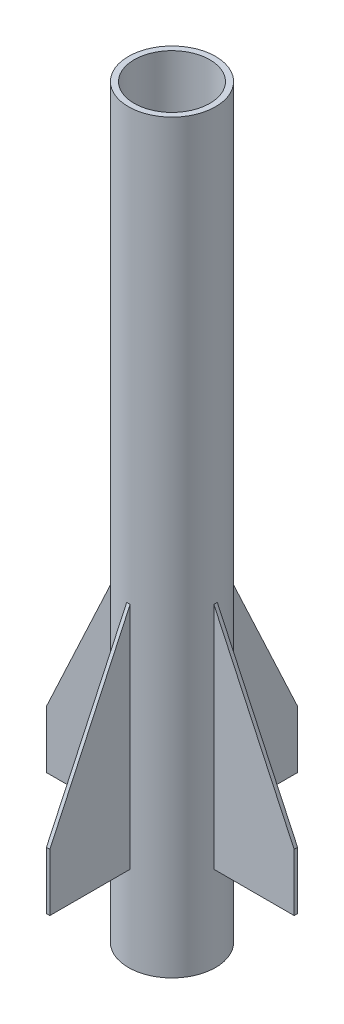
SolidWorks part; units mm, degrees
ref_plane "Front Plane" through (0, 0, 0) normal (0, 0, 1) x (1, 0, 0)
ref_plane "Top Plane" through (0, 0, 0) normal (0, 1, 0) x (1, 0, 0)
ref_plane "Right Plane" through (0, 0, 0) normal (1, 0, 0) x (0, 0, -1)
sketch "Sketch1" plane through (0, 0, 0) normal (0, 0, 1) x (1, 0, 0)
  line L0 (76, 0) -> (76, 1300)
  line L1 (0, 0) -> (0, 2000) construction
  line L9 (66, 0) -> (66, 1300)
  line L10 (76, 0) -> (66, 0)
  line L11 (76, 1300) -> (66, 1300)
  point P7 (65, 1600)
  point P8 (-1029.1667, 1600)
  point P9 (-9.3208, 1996.3774)
  dimension "D1" = 1300
  dimension "D2" = 76
  dimension "D3" = 2000
  dimension "D4" = 10
revolve "Revolve1" add sketch "Sketch1" angle 360 about L1
sketch "Sketch2" plane through (0, 0, 0) normal (0, 0, 1) x (1, 0, 0)
  line L5 (-76, 550) -> (-76, 150)
  line L6 (-76, 1300) -> (-76, 0) construction
  line L7 (-76, 150) -> (-216, 150)
  line L8 (-216, 150) -> (-216, 250)
  line L9 (-216, 250) -> (-76, 550)
  dimension "D1" = 400
  dimension "D2" = 140
  dimension "D3" = 100
  dimension "D4" = 150
extrude "Boss-Extrude1" add sketch "Sketch2" along normal blind 3 and the other way blind 3 separate body contours L9 L5 L7 L8
sketch "Sketch4" plane through (-76, 0, 0) normal (1, 0, 0) x (0, 0, -1)
  line L0 (3, 150) -> (-3, 150) construction
  line L1 (3, 550) -> (3, 150) construction
  line L2 (3, 550) -> (-3, 550) construction
  line L3 (-3, 550) -> (-3, 150) construction
  line L4 (3, 150) -> (-3, 150)
  line L5 (3, 550) -> (3, 150)
  line L6 (3, 550) -> (-3, 550)
  line L7 (-3, 550) -> (-3, 150)
sketch "Sketch5" plane through (0, 0, 0) normal (0, 0, 1) x (1, 0, 0)
  line L0 (0, 0) -> (0, 930.568) construction
pattern_circular "CirPattern2" count 4 over 360 about axis through (0, 0, 0) along (0, 1, 0) of bodies 102
